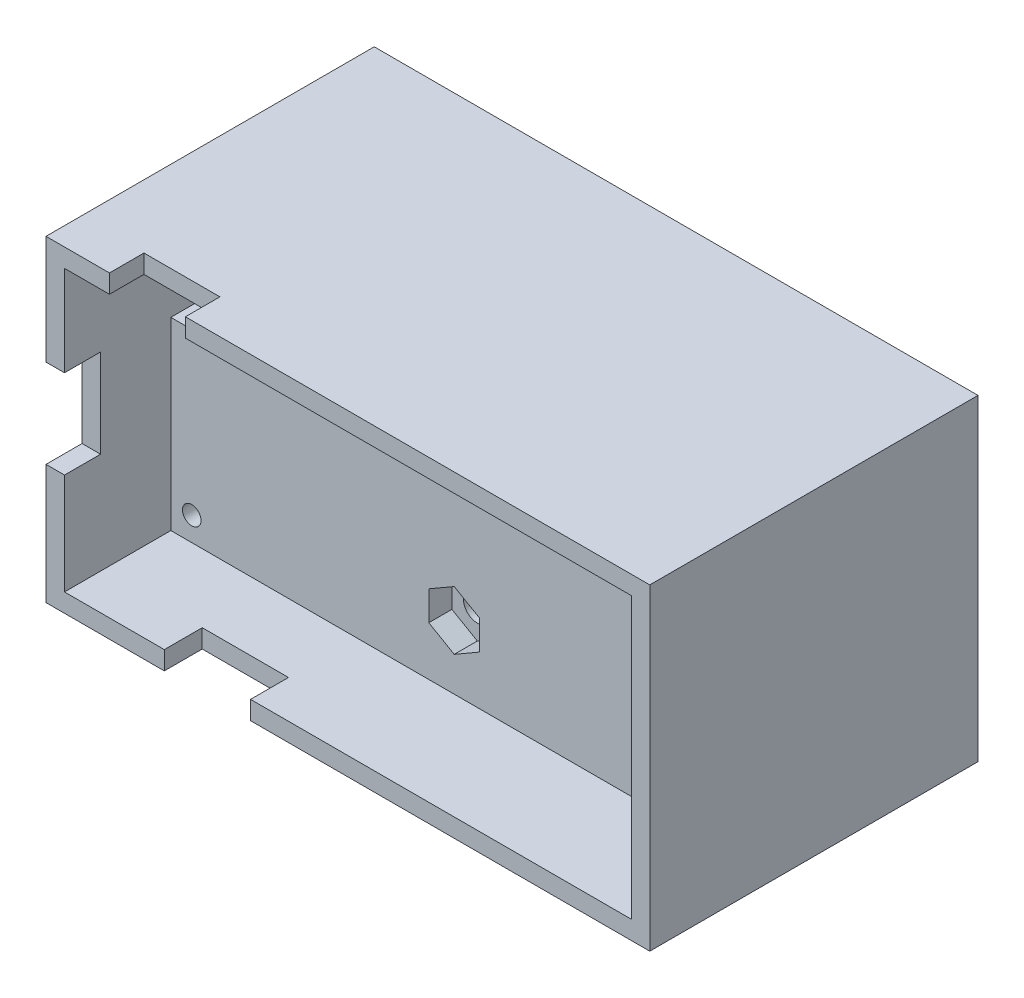
SolidWorks part; units mm, degrees
ref_plane "前视基准面" through (0, 0, 0) normal (0, 0, 1) x (1, 0, 0)
ref_plane "上视基准面" through (0, 0, 0) normal (0, 1, 0) x (1, 0, 0)
ref_plane "右视基准面" through (0, 0, 0) normal (1, 0, 0) x (0, 0, -1)
ref_plane "基准面1" through (0, 0, 3.6001) normal (0, 0, 1) x (1, 0, 0)
sketch "草图1" plane through (0, 0, 3.6001) normal (0, 0, 1) x (1, 0, 0)
  line L0 (0.8763, -38.7224) -> (-59.4234, -38.7224) construction
  line L1 (-48.7034, -33.8618) -> (-39.801, -33.8618)
  line L2 (-48.7034, -33.8618) -> (-48.7034, -38.7224)
  line L4 (-39.801, -33.8618) -> (-39.801, -38.7224)
  line L5 (-59.4234, -9.4107) -> (0.8763, -9.4107) construction
  line L7 (-55.7687, -9.4107) -> (-55.7687, -14.2907)
  line L8 (-55.7687, -14.2907) -> (-45.8066, -14.2907)
  line L9 (-45.8066, -9.4107) -> (-45.8066, -14.2907)
  line L10 (-12.699, -17.609) -> (-12.699, -12.109) construction
  line L11 (0.8763, -9.4107) -> (-45.8066, -9.4107)
  line L12 (0.8763, -9.4107) -> (0.8763, -38.7224)
  line L13 (0.8763, -38.7224) -> (-39.801, -38.7224)
  line L14 (-59.4234, -9.4107) -> (-59.4234, -19.2521)
  line L15 (-29.2736, -33.0846) -> (-20.6538, -33.0846)
  line L16 (-29.2736, -33.0846) -> (-29.2736, -36.2921)
  line L17 (-29.2736, -36.2921) -> (-20.6538, -36.2921)
  line L18 (-20.6538, -33.0846) -> (-20.6538, -36.2921)
  line L23 (-12.699, -12.109) -> (-9.399, -12.109)
  line L24 (-12.699, -12.109) -> (-12.699, -17.609)
  line L25 (-12.699, -17.609) -> (-9.399, -17.609)
  line L26 (-9.399, -12.109) -> (-9.399, -17.609)
  line L27 (-48.7034, -38.7224) -> (-59.4234, -38.7224)
  line L28 (-55.7687, -9.4107) -> (-59.4234, -9.4107)
  line L29 (-59.4234, -27.6866) -> (-59.4234, -38.7224)
  line L30 (-59.4234, -19.2521) -> (-54.3557, -19.2521)
  line L32 (-59.4234, -27.6866) -> (-54.3557, -27.6866)
  line L33 (-54.3557, -19.2521) -> (-54.3557, -27.6866)
  circle A0 centre (-57.6581, -36.6498) radius 1
  circle A1 centre (-57.6581, -11.2498) radius 1
  circle A2 centre (-1.016, -11.2498) radius 1
  circle A3 centre (-0.889, -36.8301) radius 1
  circle A4 centre (-4.1259, -29.4689) radius 1.322
  circle A5 centre (-5.9082, -27.2775) radius 0.4462
  circle A6 centre (-4.5737, -26.6799) radius 0.4462
  circle A7 centre (-3.1192, -26.8297) radius 0.4462
  circle A8 centre (-1.9345, -27.6866) radius 0.4462
  circle A9 centre (-1.3369, -29.0211) radius 0.4462
  circle A10 centre (-1.4866, -30.4756) radius 0.4462
  circle A11 centre (-2.3435, -31.6603) radius 0.4462
  circle A12 centre (-3.678, -32.2579) radius 0.4462
  circle A13 centre (-5.1325, -32.1082) radius 0.4462
  circle A14 centre (-6.3173, -31.2513) radius 0.4462
  circle A15 centre (-6.9149, -29.9168) radius 0.4462
  circle A16 centre (-6.7652, -28.4623) radius 0.4462
  point P71 (-4.1259, -29.4689)
  dimension "D1" = 12
ref_plane "基准面2" through (0, 0, -6) normal (0, 0, -1) x (-1, 0, 0)
sketch "草图2" plane through (0, 0, -6) normal (0, 0, -1) x (-1, 0, 0)
  line L0 (29.2736, -9.4107) -> (29.2736, -29.309) construction
  line L1 (-0.8763, -38.7224) -> (59.4234, -38.7224)
  line L2 (-0.8763, -38.7224) -> (-0.8763, -9.4107)
  line L3 (-0.8763, -9.4107) -> (59.4234, -9.4107)
  line L4 (59.4234, -38.7224) -> (59.4234, -9.4107)
  line L5 (59.4234, -24.0665) -> (-9.3078, -24.0665) construction
  line L9 (29.2736, -15.8165) -> (29.2736, -13.1836) construction
  line L10 (27.7854, -15.8165) -> (27.7854, -13.1836)
  line L11 (30.7617, -15.8165) -> (30.7617, -13.1836)
  line L12 (29.2736, -38.7224) -> (29.2736, -43.3487) construction
  line L14 (-3.3763, -6.9107) -> (61.9234, -6.9107)
  line L15 (-3.3763, -6.9107) -> (-3.3763, -41.2224)
  line L16 (-3.3763, -41.2224) -> (61.9234, -41.2224)
  line L17 (61.9234, -6.9107) -> (61.9234, -41.2224)
  circle A0 centre (1.016, -11.2498) radius 1
  circle A1 centre (0.889, -36.8301) radius 1
  circle A2 centre (57.6581, -36.6498) radius 1
  circle A3 centre (57.6581, -11.2498) radius 0.9222
  arc A10 (27.7854, -15.8165) -> (30.7617, -15.8165) centre (29.2736, -15.8165) ccw
  arc A11 (30.7617, -13.1836) -> (27.7854, -13.1836) centre (29.2736, -13.1836) ccw
  circle A12 centre (29.2736, -32.3165) radius 1.5
  point P27 (29.2736, -31.5665)
  point P33 (29.2736, -14.5001)
  dimension "D1" = 2.5
  dimension "D2" = 2.5
  dimension "D3" = 3
  dimension "D4" = 8.25
  dimension "D5" = 2.5
  dimension "D6" = 2.5
  dimension "D7" = 8.25
extrude "凸台-拉伸2" add sketch "草图2" along normal blind 4.5 separate body contours L17 L14 L15 L16 L4 L1 L2 L3 | L1 L4 L3 L2 A11 L11 A10 L10 A3 A2 A1 A0 region at (-29.281, -24.1116, -6) region at (-29.2736, -7.6484, -6)
sketch "草图3" plane through (0, 0, -6) normal (0, 0, -1) x (-1, 0, 0)
  line L0 (29.2736, -15.8165) -> (29.2736, -10.8487) construction
  line L1 (32.0236, -17.4043) -> (32.0236, -14.2288)
  line L4 (26.5236, -14.2288) -> (26.5236, -17.4043)
  line L5 (26.5236, -17.4043) -> (29.2736, -18.992)
  line L6 (29.2736, -18.992) -> (32.0236, -17.4043)
  line L8 (32.0236, -14.9203) -> (32.0236, -11.7449)
  line L9 (32.0236, -11.7449) -> (29.2736, -10.1572)
  line L10 (29.2736, -10.1572) -> (26.5236, -11.7449)
  line L11 (26.5236, -11.7449) -> (26.5236, -14.9203)
  line L14 (31.8974, -14.9932) -> (32.0236, -14.9203) [skipped]
  line L15 (29.2736, -22.4541) -> (17.663, -22.4541) construction
  line L16 (29.2736, -22.4541) -> (29.2736, -17.3047) construction
  line L17 (26.6497, -14.156) -> (26.5236, -14.2288) [skipped]
  line L18 (26.5236, -14.9203) -> (26.6497, -14.9932) [skipped]
  line L19 (32.0236, -14.2288) -> (31.8974, -14.156) [skipped]
  line L20 (26.5236, -33.9043) -> (29.2736, -35.492)
  line L21 (29.2736, -35.492) -> (32.0236, -33.9043)
  line L22 (32.0236, -33.9043) -> (32.0236, -30.7288)
  line L23 (32.0236, -30.7288) -> (29.2736, -29.1411)
  line L24 (29.2736, -29.1411) -> (26.5236, -30.7288)
  line L25 (26.5236, -30.7288) -> (26.5236, -33.9043)
  arc A0 (26.82, -14.5746) -> (31.7271, -14.5746) centre (29.2736, -15.8165) ccw construction
  arc A1 (31.7271, -14.5746) -> (26.82, -14.5746) centre (29.2736, -13.3326) ccw construction
  circle A2 centre (29.2736, -32.3165) radius 2.75 construction
  arc A5 (27.7854, -15.8165) -> (30.7617, -15.8165) centre (29.2736, -15.8165) ccw construction
  point P25 (29.2736, -33.8241)
  dimension "D1" = 5.5
extrude "切除-拉伸2" cut sketch "草图3" along normal blind 2.5 contours L10 L11 L4 L5 L6 L1 L8 L9 | L24 L25 L20 L21 L22 L23 region at (-29.2736, -14.5746, -6) region at (-29.2736, -32.3165, -6)
sketch "草图5" plane through (0, 0, -10.5) normal (0, 0, -1) x (-1, 0, 0)
  line L1 (-3.3763, -6.9107) -> (61.9234, -6.9107)
  line L2 (-3.3763, -6.9107) -> (-3.3763, -41.2224)
  line L3 (-3.3763, -41.2224) -> (61.9234, -41.2224)
  line L4 (61.9234, -6.9107) -> (61.9234, -41.2224)
  line L5 (-1.3763, -8.9107) -> (59.9234, -8.9107)
  line L6 (-1.3763, -8.9107) -> (-1.3763, -39.2224)
  line L7 (-1.3763, -39.2224) -> (59.9234, -39.2224)
  line L8 (59.9234, -8.9107) -> (59.9234, -39.2224)
  dimension "D1" = 2
  dimension "D2" = 2
  dimension "D3" = 2
  dimension "D4" = 2
extrude "凸台-拉伸3" add sketch "草图5" along normal blind 15.5 and the other way blind 16
sketch "草图7" plane through (0, -6.9107, 0) normal (0, 1, 0) x (1, 0, 0)
  line L0 (-41.7981, -5.5601) -> (-46.8481, -5.5601) construction
  line L1 (-55.0622, -1.765) -> (-46.8481, -1.765)
  line L2 (-55.0622, -1.765) -> (-55.0622, -5.5601)
  line L3 (-55.0622, -5.5601) -> (-46.8481, -5.5601)
  line L4 (-46.8481, -1.765) -> (-46.8481, -5.5601)
extrude "切除-拉伸4" cut sketch "草图7" against normal blind 3
sketch "草图8" plane through (-61.9234, 0, 0) normal (-1, 0, 0) x (0, 0, 1)
  line L0 (5.6001, -27.6866) -> (5.6001, -38.7224) construction
  line L1 (1.6001, -18.6953) -> (5.6001, -18.6953)
  line L2 (1.6001, -18.6953) -> (1.6001, -28.2708)
  line L3 (1.6001, -28.2708) -> (5.6001, -28.2708)
  line L4 (5.6001, -18.6953) -> (5.6001, -28.2708)
  dimension "D1" = 4
extrude "切除-拉伸5" cut sketch "草图8" against normal blind 3
sketch "草图9" plane through (0, -41.2224, 0) normal (0, -1, 0) x (1, 0, 0)
  line L0 (-59.4234, 5.6001) -> (-48.7034, 5.6001) construction
  line L1 (-49.1273, 5.6001) -> (-39.801, 5.6001)
  line L2 (-49.1273, 5.6001) -> (-49.1273, 1.3978)
  line L3 (-49.1273, 1.3978) -> (-39.801, 1.3978)
  line L4 (-39.801, 5.6001) -> (-39.801, 1.3978)
extrude "切除-拉伸6" cut sketch "草图9" against normal blind 3
sketch "草图10" plane through (0, 0, -26) normal (0, 0, -1) x (-1, 0, 0)
  line L0 (29.2736, -8.9107) -> (29.2736, -43.7563) construction
  line L1 (-3.3763, -6.9107) -> (61.9234, -6.9107)
  line L2 (-3.3763, -6.9107) -> (-3.3763, -41.2224)
  line L3 (-3.3763, -41.2224) -> (61.9234, -41.2224)
  line L4 (61.9234, -6.9107) -> (61.9234, -41.2224)
  line L5 (-1.3763, -8.9107) -> (59.9234, -8.9107)
  line L6 (-1.3763, -8.9107) -> (-1.3763, -39.2224)
  line L7 (-1.3763, -39.2224) -> (59.9234, -39.2224)
  line L8 (59.9234, -8.9107) -> (59.9234, -39.2224)
  line L9 (-1.3763, -24.0665) -> (74.3166, -24.0665) construction
  circle A0 centre (1.016, -11.2498) radius 1
  arc A1 (-1.3763, -14.9107) -> (4.6237, -8.9107) centre (-1.3763, -8.9107) ccw
  circle A2 centre (57.6581, -11.2498) radius 1
  arc A3 (53.9234, -8.9107) -> (59.9234, -14.9107) centre (59.9234, -8.9107) ccw
  circle A4 centre (57.6581, -36.8833) radius 1
  arc A5 (53.9234, -39.2224) -> (59.9234, -33.2224) centre (59.9234, -39.2224) cw
  circle A6 centre (1.016, -36.8833) radius 1
  arc A7 (-1.3763, -33.2224) -> (4.6237, -39.2224) centre (-1.3763, -39.2224) cw
  line M2 (-3.3763, -6.9107) -> (-3.3763, -41.2224)
  line M3 (-3.3763, -41.2224) -> (61.9234, -41.2224)
  line M4 (61.9234, -41.2224) -> (61.9234, -6.9107)
  line M5 (61.9234, -6.9107) -> (-3.3763, -6.9107)
  line M6 (59.9234, -39.2224) -> (-1.3763, -39.2224)
  line M7 (-1.3763, -39.2224) -> (-1.3763, -8.9107)
  line M8 (-1.3763, -8.9107) -> (59.9234, -8.9107)
  line M9 (59.9234, -8.9107) -> (59.9234, -39.2224)
  dimension "D1" = 6
  dimension "D2" = 6
  dimension "D3" = 2
  dimension "D4" = 2
extrude "凸台-拉伸4" add sketch "草图10" along normal blind 4 contours L8 L7 L6 L5 M5 M2 M3 M4 M9 M6 M7 M8 | L6 A1 A0 M8 | A7 A6 M7 M6 | A5 A4 M6 M9 | A3 A2 M8 M9 region at (-29.2736, -7.6484, -26) region at (-1.6237, -8.9956, -26) region at (-56.9234, -8.9956, -26) region at (-2.8063, -35.0397, -26) region at (-59.8386, -36.2224, -26)
sketch "草图11" plane through (0, 0, -30) normal (0, 0, -1) x (-1, 0, 0)
  line L1 (-3.3763, -6.9107) -> (61.9234, -6.9107)
  line L2 (-3.3763, -6.9107) -> (-3.3763, -41.2224)
  line L3 (-3.3763, -41.2224) -> (61.9234, -41.2224)
  line L4 (61.9234, -6.9107) -> (61.9234, -41.2224)
  circle A0 centre (1.016, -11.2498) radius 1
  circle A1 centre (1.016, -36.8833) radius 1
  circle A2 centre (57.6581, -36.8833) radius 1
  circle A3 centre (57.6581, -11.2498) radius 1
sketch "草图13" plane through (0, 0, -6) normal (0, 0, 1) x (1, 0, 0)
  line L0 (-59.9234, -18.6953) -> (-59.9234, -8.9107) construction
  line L1 (-59.9234, -13.803) -> (-55.6885, -13.803)
  line L2 (-59.9234, -13.803) -> (-59.9234, -19.2521)
  line L3 (-59.9234, -19.2521) -> (-55.6885, -19.2521)
  line L4 (-55.6885, -13.803) -> (-55.6885, -19.2521)
  line L5 (-59.4234, -19.2521) -> (-54.3557, -19.2521) construction
  point P8 (-59.9234, -19.2521)
  dimension "D1" = 4.2349
extrude "切除-拉伸7" cut sketch "草图13" against normal blind 10
